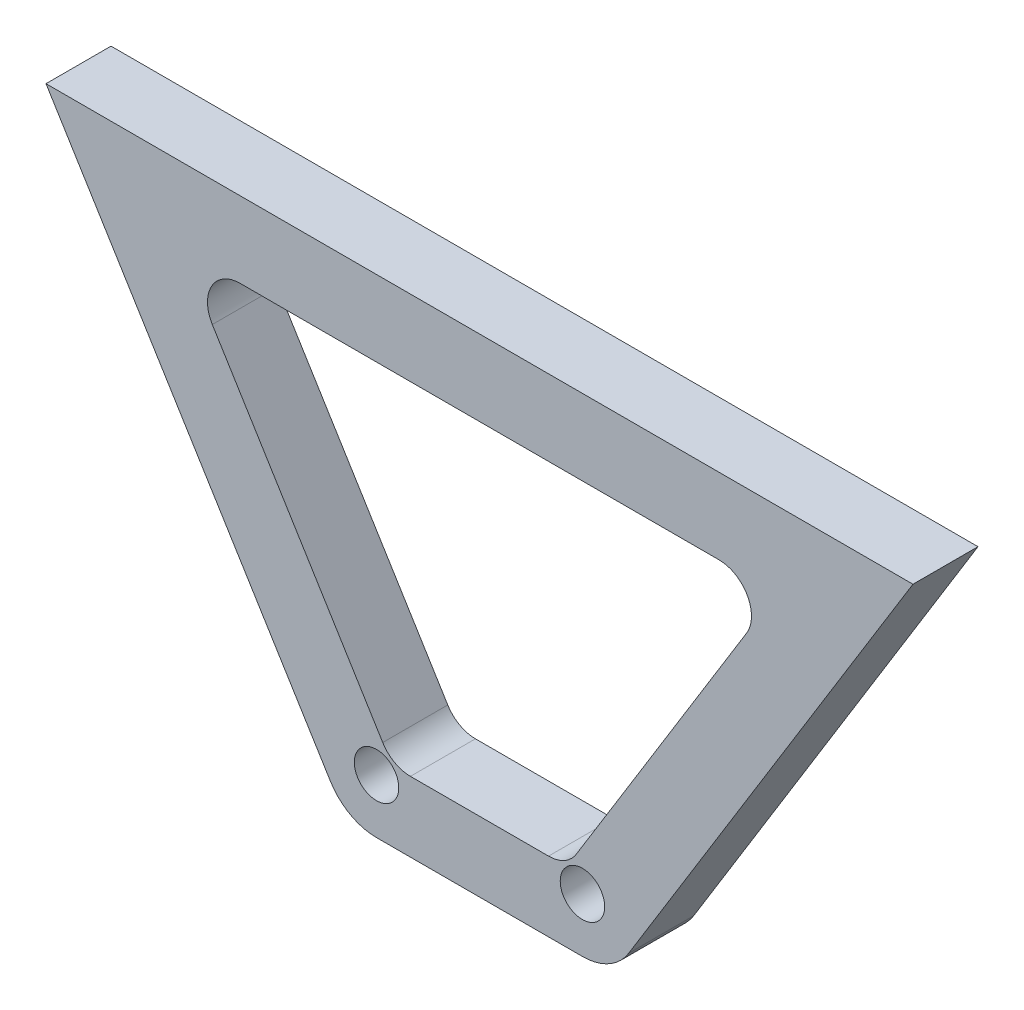
SolidWorks part; units mm, degrees
material "Клен"
ref_plane "Спереди" through (0, 0, 0) normal (0, 0, 1) x (1, 0, 0)
ref_plane "Сверху" through (0, 0, 0) normal (0, 1, 0) x (1, 0, 0)
ref_plane "Справа" through (0, 0, 0) normal (1, 0, 0) x (0, 0, -1)
sketch "Эскиз1" plane through (0, 0, 0) normal (0, 0, 1) x (1, 0, 0)
  line L0 (-40, 0) -> (40, 0)
  line L2 (0, -62.2549) -> (0, 44.8529) construction
  line L4 (-9.5, -45) -> (9.5, -45)
  line L5 (-13.7577, -42.6215) -> (-40, 0)
  line L6 (13.7577, -42.6215) -> (40, 0)
  line L7 (-22.0995, -7) -> (22.0995, -7)
  line L8 (24.6541, -11.5729) -> (8.9284, -37.1137)
  line L9 (6.3738, -38.5408) -> (-6.3738, -38.5408)
  line L10 (-8.9284, -37.1137) -> (-24.6541, -11.5729)
  arc A0 (9.5, -45) -> (13.7577, -42.6215) centre (9.5, -40) ccw
  arc A1 (-9.5, -45) -> (-13.7577, -42.6215) centre (-9.5, -40) cw
  circle A2 centre (-9.5, -40) radius 2.05
  circle A3 centre (9.5, -40) radius 2.05
  arc A4 (8.9284, -37.1137) -> (6.3738, -38.5408) centre (6.3738, -35.5408) cw
  arc A5 (-6.3738, -38.5408) -> (-8.9284, -37.1137) centre (-6.3738, -35.5408) cw
  arc A6 (22.0995, -7) -> (24.6541, -11.5729) centre (22.0995, -10) cw
  arc A7 (-22.0995, -7) -> (-24.6541, -11.5729) centre (-22.0995, -10) ccw
  point P7 (0, 0)
  point P9 (0, -45)
  point P13 (12.2932, -45)
  point P16 (-12.2932, -45)
  dimension "D3" = 5
  dimension "D4" = 4.1
  dimension "D9" = 3
  dimension "D2" = 80
  dimension "D5" = 9.5
  dimension "D6" = 45
  dimension "D1" = 7
  dimension "D7" = 7
  dimension "D8" = 7
extrude "Бобышка-Вытянуть1" add sketch "Эскиз1" along normal blind 6
ref_plane "Плоскость1" through (0, 0, 0) normal (1, 0, 0) x (0, 0, -1)
equation "\"D8@Эскиз1\"=\"D7@Эскиз1\""
